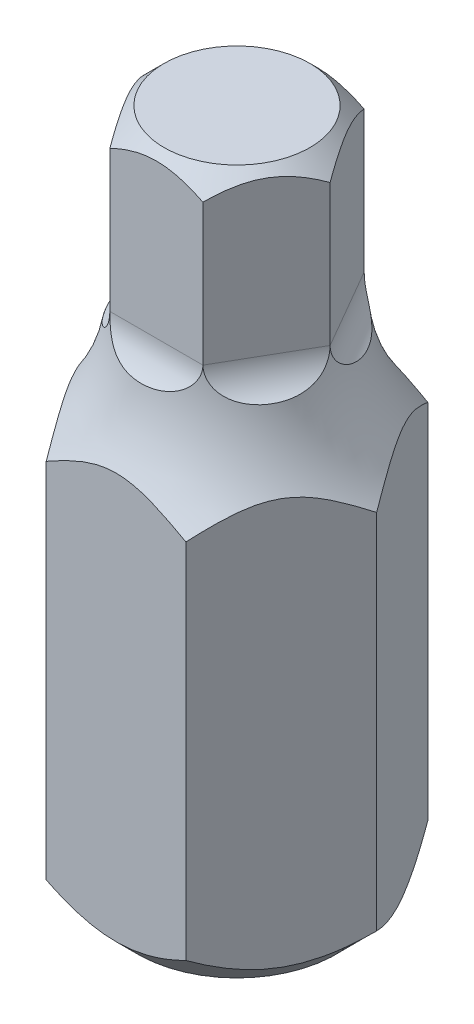
SolidWorks part; units mm, degrees
material "Stainless Steel (ferritic)"
ref_plane "Front Plane" through (0, 0, 0) normal (0, 0, 1) x (1, 0, 0)
ref_plane "Top Plane" through (0, 0, 0) normal (0, 1, 0) x (1, 0, 0)
ref_plane "Right Plane" through (0, 0, 0) normal (1, 0, 0) x (0, 0, -1)
sketch "Sketch1" plane through (0, 0, 0) normal (0, 1, 0) x (1, 0, 0)
  line L1 (3.4641, 0) -> (1.7321, 3)
  line L2 (1.7321, 3) -> (-1.7321, 3)
  line L3 (-1.7321, 3) -> (-3.4641, 0)
  line L4 (-3.4641, 0) -> (-1.7321, -3)
  line L5 (-1.7321, -3) -> (1.7321, -3)
  line L6 (1.7321, -3) -> (3.4641, 0)
  line L7 (1.1547, -2) -> (2.3094, 0)
  line L8 (2.3094, 0) -> (1.1547, 2)
  line L9 (1.1547, 2) -> (-1.1547, 2)
  line L10 (-1.1547, 2) -> (-2.3094, 0)
  line L11 (-2.3094, 0) -> (-1.1547, -2)
  line L12 (-1.1547, -2) -> (1.1547, -2)
  circle A0 centre (0, 0) radius 3 construction
  circle A1 centre (0, 0) radius 2 construction
  dimension "D1" = 6
  dimension "D2" = 4
extrude "Boss-Extrude2" add sketch "Sketch1" along normal blind 17 contours L7 L8 L9 L10 L11 L12
extrude "Boss-Extrude3" add sketch "Sketch1<3>" along normal blind 12
sketch "Sketch1<3>" plane through (0, 0, 0) normal (0, 1, 0) x (1, 0, 0) same geometry as "Sketch1"
fillet "Fillet1" radius 1 6 edges at (1.7321, 12, -1) (0, 12, -2) (-1.7321, 12, -1) (-1.7321, 12, 1) (0, 12, 2) (1.7321, 12, 1)
sketch "Sketch3" plane through (0, 0, 0) normal (0, 0, 1) x (1, 0, 0)
  line L0 (-2.3094, 17) -> (-1.8094, 17)
  line L1 (-2.3094, 17) -> (-1.1547, 17) construction
  line L2 (-1.8094, 17) -> (-2.3094, 16.5)
  line L3 (-2.3094, 17) -> (-2.3094, 13) construction
  line L4 (-2.3094, 16.5) -> (-2.3094, 17)
  line L5 (-3.4641, 0) -> (-2.4641, 0)
  line L6 (-3.4641, 0) -> (-1.7321, 0) construction
  line L7 (-2.4641, 0) -> (-3.4641, 1)
  line L8 (-3.4641, 12) -> (-3.4641, 0) construction
  line L9 (-3.4641, 1) -> (-3.4641, 0)
  line L10 (0, 0) -> (0, 50000) construction
  circle A0 centre (-6.8094, 13) radius 4.5
  dimension "D4" = 9
  dimension "D1" = 0.5
  dimension "D2" = 45
  dimension "D3" = 4
  dimension "D5" = 1
  dimension "D6" = 45
revolve "Cut-Revolve1" cut sketch "Sketch3" angle 360 about L10
